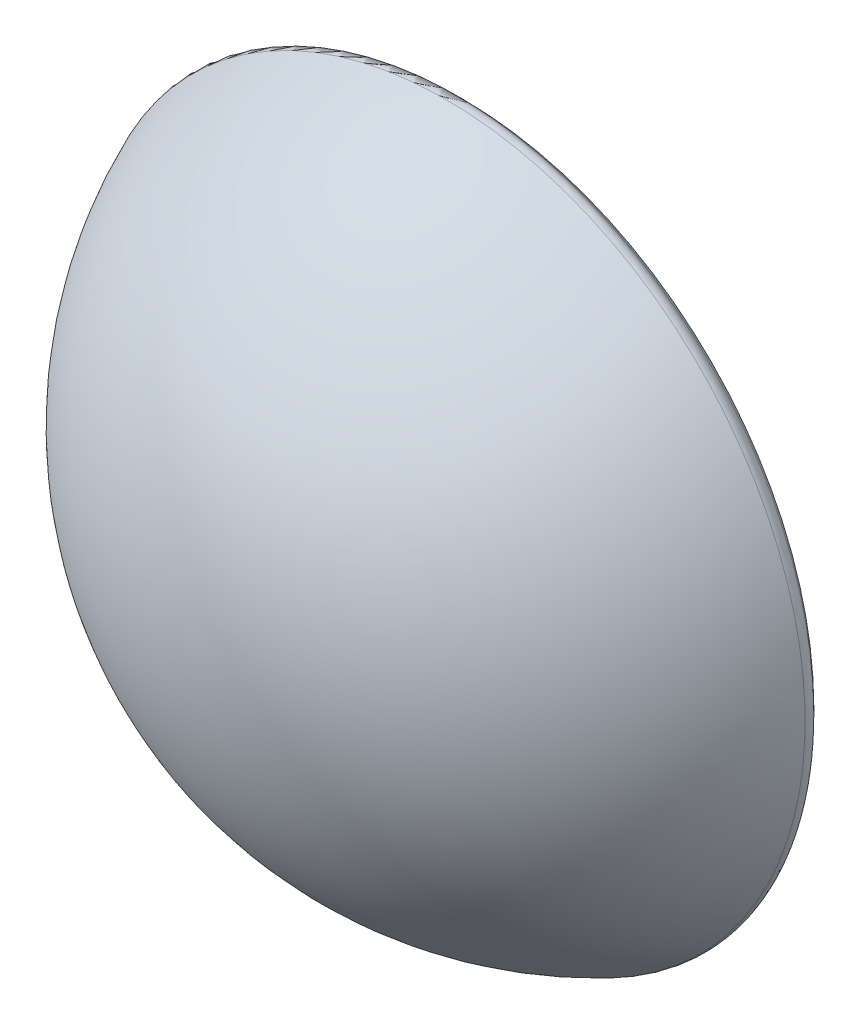
SolidWorks part; units mm, degrees
ref_plane "Front Plane" through (0, 0, 0) normal (0, 0, 1) x (1, 0, 0)
ref_plane "Top Plane" through (0, 0, 0) normal (0, 1, 0) x (1, 0, 0)
ref_plane "Right Plane" through (0, 0, 0) normal (1, 0, 0) x (0, 0, -1)
ref_axis "Axis1" through (0, 0, 27.2475) along (0, 0, -1)
sketch "Sketch1" plane through (0, 0, 0) normal (0, 0, 1) x (1, 0, 0)
  circle A0 centre (0, 0) radius 31.75
  dimension "D1" = 63.5
extrude "Boss-Extrude1" add sketch "Sketch1" along normal blind 13
fillet "Fillet1" radius 5 1 edges at (31.75, 0, 13)
ref_plane "Plane2" through (0, 0, 8) normal (0, 0, 1) x (1, 0, 0)
sketch "Sketch12" plane through (0, 0, 0) normal (0, 1, 0) x (1, 0, 0)
  line L0 (0, -8) -> (33.2, -8) construction
  line L1 (-55, -8) -> (55, -8) construction
  line L2 (0, -27.2475) -> (0, 1.2975) construction
  line L3 (0, -25.95) -> (0, -11.6)
  line L4 (0, -11.6) -> (27.2428, -11.6)
  line L5 (37.2275, 0) -> (30.35, 0)
  line L6 (30.35, 0) -> (30.35, -8)
  line L7 (-26.75, -13) -> (26.75, -13) construction
  line L8 (31.75, -8) -> (31.75, 0) construction
  line L9 (30.35, -8) -> (27.2428, -8) construction
  line L10 (27.2428, -8) -> (27.2428, -11.2313) construction
  line L11 (27.2428, -11.1072) -> (27.2428, -11.6)
  arc A0 (39.678, 13.728) -> (0, -25.95) centre (0, 13.728) cw construction
  arc A1 (30.35, -8) -> (27.2428, -11.1072) centre (27.2428, -8) cw
  arc A2 (0, -25.95) -> (37.2275, 0) centre (0, 13.728) ccw
  point P4 (0, 13.728)
  dimension "D1" = 33.2
  dimension "D2" = 1.4
  dimension "D3" = 1.4
revolve "Revolve3" add sketch "Sketch12" angle 360 about axis through (0, 0, 27.2475) along (0, 0, -1) region at (14.7014, 0, 15.6485)
shell "Shell1" thickness 1.5 removed face at (37.2275, 0, 0)
sketch "Sketch9" plane through (0, 0, 0) normal (0, 0, -1) x (-1, 0, 0)
  circle A0 centre (0, 0) radius 35.6245
  circle A1 centre (0, 0) radius 27.25
  circle A3 centre (0, 0) radius 35.6245 construction
  dimension "D2" = 54.5
extrude "Boss-Extrude5" add sketch "Sketch9" against normal blind 2
sketch "Sketch2" plane through (0, 0, 0) normal (0, 0, -1) x (-1, 0, 0)
  line L0 (0, 0) -> (-31.75, 0) construction
  line L1 (-30.8515, -7.5) -> (-23.5, -7.5)
  line L2 (-30.8515, 7.5) -> (-23.5, 7.5)
  line L3 (-23.5, 7.5) -> (-23.5, -7.5)
  line L4 (-30.8515, -7.5) -> (-30.8515, 7.5)
  line L5 (8.9305, 30.4681) -> (5.2548, 24.1016)
  line L6 (21.9209, 22.9681) -> (18.2452, 16.6016)
  line L7 (18.2452, 16.6016) -> (5.2548, 24.1016)
  line L8 (8.9305, 30.4681) -> (21.9209, 22.9681)
  line L9 (21.9209, -22.9681) -> (18.2452, -16.6016)
  line L10 (8.9305, -30.4681) -> (5.2548, -24.1016)
  line L11 (5.2548, -24.1016) -> (18.2452, -16.6016)
  line L12 (21.9209, -22.9681) -> (8.9305, -30.4681)
  circle A1 centre (0, 0) radius 23.5 construction
  point P10 (0, 0)
  point P22 (0, 0)
  dimension "D2" = 47
  dimension "D1" = 7.5
  dimension "D5" = 23.5
  dimension "D6" = 7.3515
  dimension "D3" = 3
extrude "Boss-Extrude2" add sketch "Sketch2" against normal blind 2
sketch "Sketch4" plane through (0, 0, 2) normal (0, 0, 1) x (1, 0, 0)
  line L0 (23.5, 5) -> (23.5, -5) construction
  line L1 (23.5, 7.5) -> (34.4266, 7.5)
  line L2 (23.5, 7.5) -> (23.5, 5)
  line L3 (23.5, 5) -> (34.4266, 5)
  line L4 (34.4266, 7.5) -> (34.4266, 5)
  line L5 (23.5, -7.5) -> (34.4266, -7.5)
  line L6 (23.5, -7.5) -> (23.5, -5)
  line L7 (23.5, -5) -> (34.4266, -5)
  line L8 (34.4266, -7.5) -> (34.4266, -5)
  line L9 (-16.0801, -17.8516) -> (-21.5434, -27.3143)
  line L10 (-18.2452, -16.6016) -> (-16.0801, -17.8516)
  line L11 (-18.2452, -16.6016) -> (-23.7085, -26.0643)
  line L12 (-23.7085, -26.0643) -> (-21.5434, -27.3143)
  line L13 (-7.4199, -22.8516) -> (-16.0801, -17.8516) construction
  line L14 (-7.4199, -22.8516) -> (-12.8832, -32.3143)
  line L15 (-5.2548, -24.1016) -> (-7.4199, -22.8516)
  line L16 (-5.2548, -24.1016) -> (-10.7181, -33.5643)
  line L17 (-10.7181, -33.5643) -> (-12.8832, -32.3143)
  line L18 (-7.4199, 22.8516) -> (-12.8832, 32.3143)
  line L19 (-5.2548, 24.1016) -> (-7.4199, 22.8516)
  line L20 (-5.2548, 24.1016) -> (-10.7181, 33.5643)
  line L21 (-10.7181, 33.5643) -> (-12.8832, 32.3143)
  line L22 (-16.0801, 17.8516) -> (-7.4199, 22.8516) construction
  line L23 (-16.0801, 17.8516) -> (-21.5434, 27.3143)
  line L24 (-18.2452, 16.6016) -> (-16.0801, 17.8516)
  line L25 (-18.2452, 16.6016) -> (-23.7085, 26.0643)
  line L26 (-23.7085, 26.0643) -> (-21.5434, 27.3143)
  line L27 (0, 0) -> (23.5, 0) construction
  circle A2 centre (0, 0) radius 34.7878 construction
  point P10 (23.5, 0)
  point P24 (-11.75, -20.3516)
  point P32 (-0.0257, -0.0149)
  point P34 (-11.75, 20.3516)
  dimension "D1" = 2.5
  dimension "D2" = 2.5
  dimension "D3" = 23.5
extrude "Boss-Extrude3" add sketch "Sketch4" along normal up to next
fillet "Fillet2" [suppressed] radius 1
fillet "Fillet3" radius 1 6 edges at (23.5, 7.5, 7.7053) (23.5, -7.5, 7.7053) (-18.2452, -16.6016, 7.7053) (-5.2548, -24.1016, 7.7053) (-18.2452, 16.6016, 7.7053) (-5.2548, 24.1016, 7.7053)
ref_plane "Plane1" through (0, 0, 5) normal (0, 0, -1) x (-1, 0, 0)
sketch "Sketch5" plane through (0, 0, 0) normal (0, 0, -1) x (-1, 0, 0)
  line L0 (0, 0) -> (37.6561, 0) construction
  line L1 (34.7878, -4) -> (34.7878, 4)
  line L2 (34.7878, 4) -> (24, 4)
  line L3 (24, 4) -> (24, -4)
  line L4 (24, -4) -> (34.7878, -4)
  line L5 (-8.5359, -22.7846) -> (-15.4641, -18.7846)
  line L6 (-13.9298, -32.1271) -> (-8.5359, -22.7846)
  line L7 (-20.858, -28.1271) -> (-13.9298, -32.1271)
  line L8 (-15.4641, -18.7846) -> (-20.858, -28.1271)
  line L9 (-15.4641, 18.7846) -> (-8.5359, 22.7846)
  line L10 (-20.858, 28.1271) -> (-15.4641, 18.7846)
  line L11 (-13.9298, 32.1271) -> (-20.858, 28.1271)
  line L12 (-8.5359, 22.7846) -> (-13.9298, 32.1271)
  circle A1 centre (0, 0) radius 24 construction
  arc A2 (23.4801, -25.6686) -> (23.4801, 25.6686) centre (0, 0) ccw construction
  point P3 (34.7878, 0)
  point P6 (24, 0)
  point P22 (0, 0)
  dimension "D2" = 48
  dimension "D1" = 8
  dimension "D3" = 3
extrude "Boss-Extrude4" add sketch "Sketch5" against normal up to next
sketch "Sketch6" plane through (-24, 0, 0) normal (1, 0, 0) x (0, 0, -1)
  line L0 (0, 4) -> (0, -4) construction
  line L1 (-5, 2) -> (-7, 2)
  line L2 (-5, 2) -> (-5, -2)
  line L3 (-5, -2) -> (-7, -2)
  line L4 (-7, 2) -> (-7, -2)
  line L5 (0, 0) -> (-10.1656, 0) construction
  point P10 (-7, 0)
  dimension "D1" = 5
  dimension "D2" = 2
  dimension "D3" = 4
extrude "Cut-Extrude1" cut sketch "Sketch6" against normal blind 4
sketch "Sketch7" plane through (12, -20.7846, 0) normal (-0.5, 0.866, 0) x (0.866, 0.5, 0)
  line L0 (-4, 0) -> (4, 0) construction
  line L1 (-2, -5) -> (2, -5)
  line L2 (-2, -5) -> (-2, -7)
  line L3 (-2, -7) -> (2, -7)
  line L4 (2, -5) -> (2, -7)
  line L5 (0, 0) -> (0, -10.1651) construction
  point P10 (0, -7)
  dimension "D1" = 5
  dimension "D2" = 2
  dimension "D3" = 4
extrude "Cut-Extrude2" cut sketch "Sketch7" against normal blind 4
sketch "Sketch8" plane through (12, 20.7846, 0) normal (-0.5, -0.866, 0) x (0.866, -0.5, 0)
  line L0 (4, 0) -> (-4, 0) construction
  line L1 (2, 5) -> (-2, 5)
  line L2 (2, 5) -> (2, 7)
  line L3 (2, 7) -> (-2, 7)
  line L4 (-2, 5) -> (-2, 7)
  line L5 (0, 0) -> (0, 10.1651) construction
  point P10 (0, 7)
  dimension "D1" = 5
  dimension "D2" = 2
  dimension "D3" = 4
extrude "Cut-Extrude3" cut sketch "Sketch8" against normal blind 4
ref_plane "Plane3" through (0, 0, 16) normal (0, 0, -1) x (-1, 0, 0)
sketch "Sketch10" plane through (0, 0, 16) normal (0, 0, -1) x (-1, 0, 0)
  circle A0 centre (0, 0) radius 24
  dimension "D1" = 48
extrude "Boss-Extrude6" [suppressed] add sketch "Sketch10" against normal up to next
fillet "Fillet4" [suppressed] radius 1
fillet "Fillet5" radius 1 6 edges at (8.5359, 22.7846, 7.8462) (15.4641, 18.7846, 7.8462) (8.5359, -22.7846, 7.8462) (15.4641, -18.7846, 7.8462) (-24, -4, 7.8462) (-24, 4, 7.8462)
fillet "Fillet6" [suppressed] radius 2
chamfer "Chamfer1" [suppressed] distance 0.4 angle 45
chamfer "Chamfer2" distance 1.5 angle 45 1 edges at (37.2275, 0, 0) first distance on face at (0, 0, 0)
fillet "Fillet7" radius 1 1 edges at (-36.8102, 0, 1.0827)
chamfer "Chamfer3" distance 0.5 angle 45 15 edges at (25.3488, -7.5, 0) (25.3488, 7.5, 0) (23.7929, -7.2071, 0) (23.7929, 7.2071, 0) (23.5, 0, 0) (-19.1696, -18.2027, 0) (-6.1792, -25.7027, 0) (-18.138, -17.0017, 0) (-5.6549, -24.2088, 0) (-11.75, -20.3516, 0) (-6.1792, 25.7027, 0) (-19.1696, 18.2027, 0) (-5.6549, 24.2088, 0) (-18.138, 17.0017, 0) (-11.75, 20.3516, 0)
fillet "Fillet8" [suppressed] radius 1
sketch "Sketch11" plane through (0, 0, 0) normal (0, 1, 0) x (1, 0, 0)
  line L0 (0, -27.2475) -> (0, 1.2975) construction
  line L1 (-34.925, -8) -> (34.925, -8) construction
  line L5 (0, -39.75) -> (0, -8)
  line L6 (0, -8) -> (31.75, -8)
  circle A0 centre (0, -8) radius 31.75 construction
  arc A1 (31.75, -8) -> (0, -39.75) centre (0, -8) cw
  dimension "D1" = 63.5
revolve "Revolve2" [suppressed] add sketch "Sketch11" angle 360 about axis through (0, 0, 27.2475) along (0, 0, -1)
